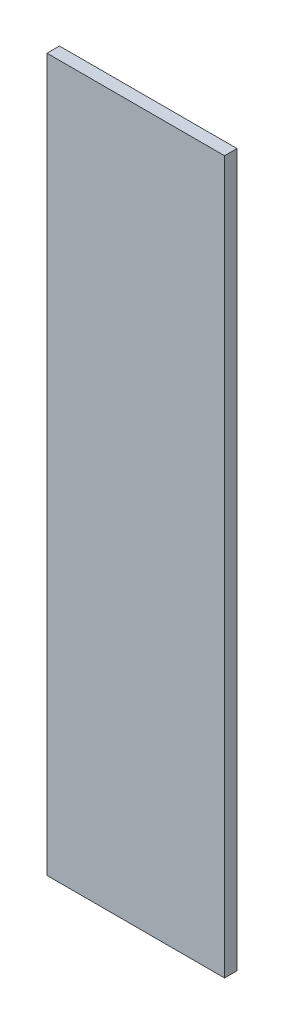
SolidWorks part; units mm, degrees
ref_plane "Front Plane" through (0, 0, 0) normal (0, 0, 1) x (1, 0, 0)
ref_plane "Top Plane" through (0, 0, 0) normal (0, 1, 0) x (1, 0, 0)
ref_plane "Right Plane" through (0, 0, 0) normal (1, 0, 0) x (0, 0, -1)
sketch "Sketch1" plane through (0, 0, 0) normal (0, 0, 1) x (1, 0, 0)
  line L1 (-92.3735, 63.8735) -> (-63.8735, 63.8735)
  line L2 (-92.3735, 63.8735) -> (-92.3735, -50.4265)
  line L3 (-92.3735, -50.4265) -> (-63.8735, -50.4265)
  line L4 (-63.8735, 63.8735) -> (-63.8735, -50.4265)
  dimension "D1" = 114.3
  dimension "D2" = 28.5
extrude "Boss-Extrude1" add sketch "Sketch1" along normal blind 2
